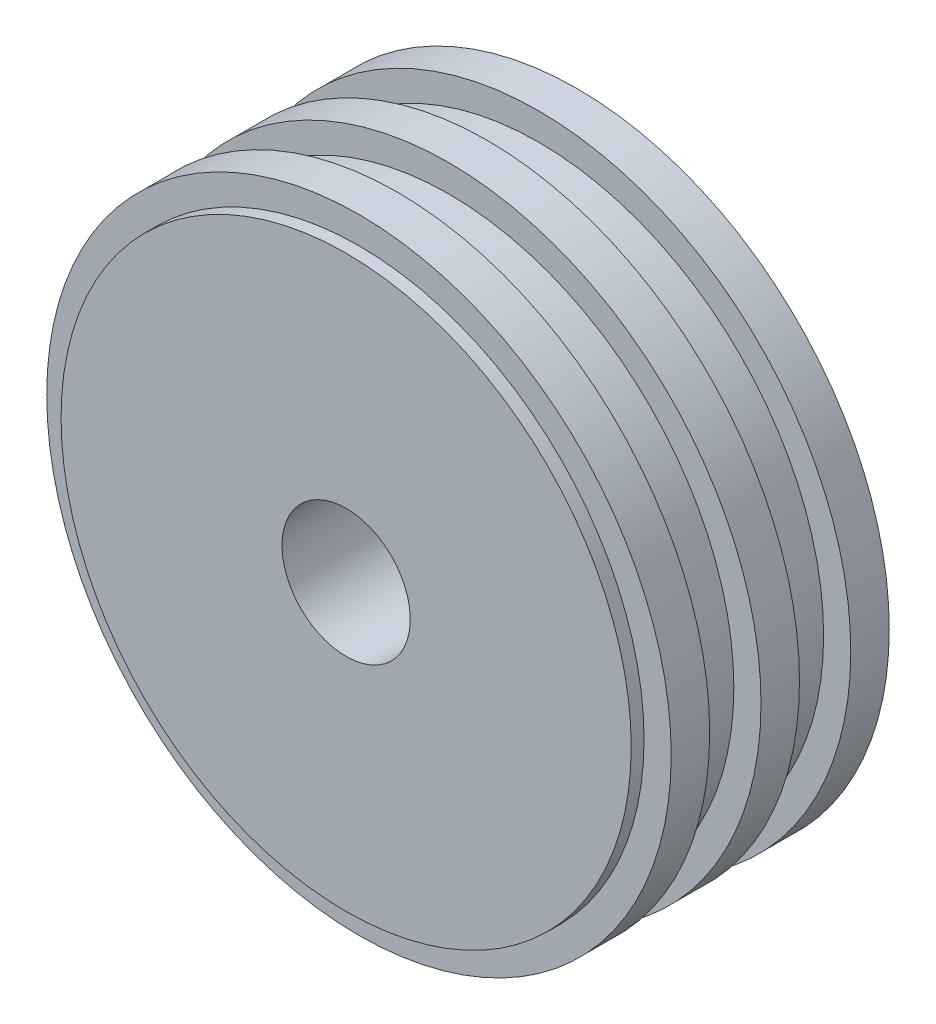
SolidWorks part; units mm, degrees
ref_plane "Front Plane" through (0, 0, 0) normal (0, 0, 1) x (1, 0, 0)
ref_plane "Top Plane" through (0, 0, 0) normal (0, 1, 0) x (1, 0, 0)
ref_plane "Right Plane" through (0, 0, 0) normal (1, 0, 0) x (0, 0, -1)
sketch "Sketch1" plane through (0, 0, 0) normal (0, 0, 1) x (1, 0, 0)
  circle A0 centre (0, 0) radius 66.675
  circle A1 centre (0, 0) radius 15
extrude "Boss-Extrude3" add sketch "Sketch1" along normal blind 57 contours A1 | A0
ref_plane "Plane2" through (0, 0, 3) normal (0, 0, -1) x (-1, 0, 0)
sketch "Sketch3" plane through (0, 0, 3) normal (0, 0, -1) x (-1, 0, 0)
  circle A0 centre (0, 0) radius 72.071
  point P3 (-47.2558, 82.9001)
sketch "Sketch4" plane through (0, 0, 3) normal (0, 0, -1) x (-1, 0, 0)
  circle A0 centre (0, 0) radius 73.025
extrude "Boss-Extrude4" add sketch "Sketch4" against normal blind 9
ref_axis "Axis1" through (0, 0, 57) along (0, 0, -1)
pattern_linear "LPattern1" count 3 spacing 21 along (0, 0, 1) of "Boss-Extrude4"
sketch "Sketch5" plane through (0, 0, 0) normal (0, 0, -1) x (-1, 0, 0)
  circle A0 centre (0, 0) radius 15
extrude "Cut-Extrude2" cut sketch "Sketch5" against normal mid plane 1000
